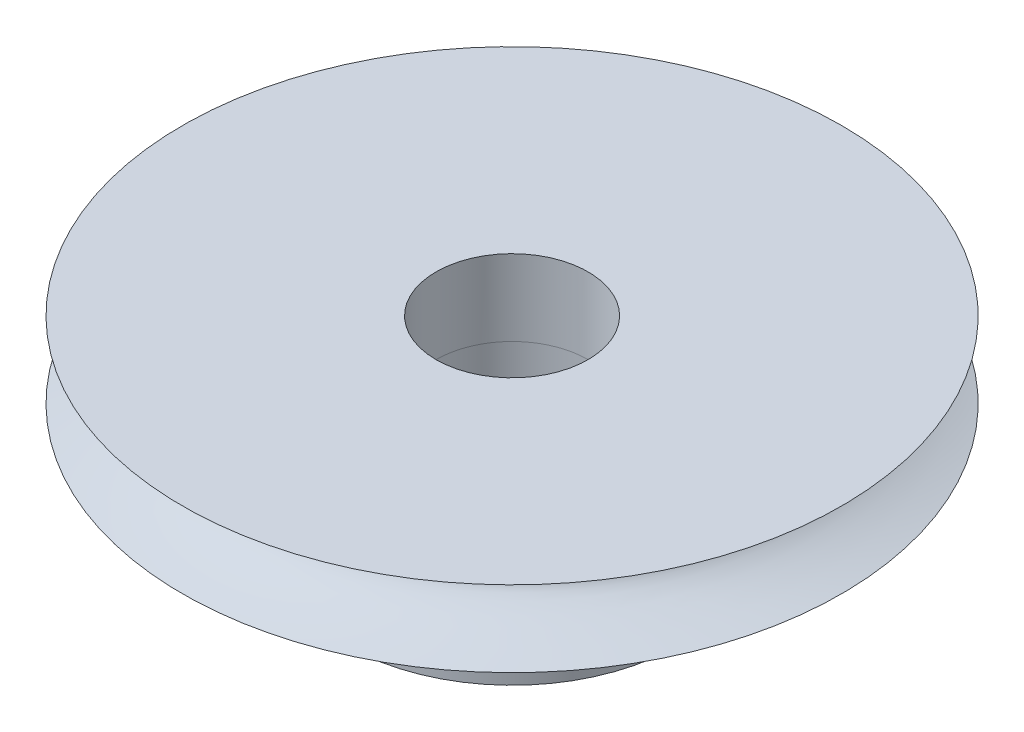
SolidWorks part; units mm, degrees
ref_plane "Front Plane" through (0, 0, 0) normal (0, 0, 1) x (1, 0, 0)
ref_plane "Top Plane" through (0, 0, 0) normal (0, 1, 0) x (1, 0, 0)
ref_plane "Right Plane" through (0, 0, 0) normal (1, 0, 0) x (0, 0, -1)
sketch "Sketch9" plane through (0, 0, 0) normal (0, 0, 1) x (1, 0, 0)
  line L0 (-4.7031, 0.0646) -> (0.1321, -1.2942) construction
  line L1 (-4.7031, -2.9354) -> (8.2969, -2.9354)
  line L3 (-4.7031, 0.0646) -> (8.2969, 0.0646)
  line L4 (8.2969, -2.9354) -> (8.2969, 0.0646)
  line L5 (0.1321, -1.2942) -> (-4.7031, -2.9354) construction
  spline S0 degree 2 poles (-4.7031, 0.0646) (0.1321, -1.2942) (-4.7031, -2.9354) knots 0 0 0 1 1 1
  dimension "D3" = 13
  dimension "D1" = 3
  dimension "D2" = 13
revolve "Revolve1" add sketch "Sketch9" angle 360 about L4
sketch "Sketch117" plane through (0, 0.0646, 0) normal (0, 1, 0) x (1, 0, 0)
  circle A0 centre (8.2969, 0) radius 3
extrude "Cut-Extrude4" cut sketch "Sketch117" against normal blind 3
sketch "Sketch122" plane through (0, -2.9354, 0) normal (0, -1, 0) x (-1, 0, 0)
  circle A0 centre (-8.2969, 0) radius 6.5398
extrude "Boss-Extrude1" add sketch "Sketch122" along normal blind 5
sketch "Sketch123" plane through (0, -2.9354, 0) normal (0, 1, 0) x (1, 0, 0)
  circle A0 centre (8.333, 0) radius 3.036
extrude "Cut-Extrude5" cut sketch "Sketch123" against normal blind 5
hole_wizard "M2x0.4 Tapped Hole1" positions "3DSketch1" profile "Sketch124" tap size "M2x0.4" standard "ANSI Metric" end condition through all
sketch3d "3DSketch1"
  circle A0 centre (8.2969, -2.9354, 0) radius 6.5398 construction
  circle A1 centre (8.2969, -7.9354, 0) radius 6.5398 construction
  point P0 (1.8154, -5.4316, -0.8709)
  point P5 (8.2969, -9.4751, 0)
  point P8 (8.2969, -14.4751, 0)
  dimension "D1" = 7
  dimension "D2" = 7.0027
sketch "Sketch124" plane through (1.8154, -5.4316, -0.8709) normal (0, 1, 0) x (-0.1332, 0, 0.9911)
  line L0 (0, 0) -> (0, 21.1551)
  line L1 (0, 21.1551) -> (0.8, 21.1551)
  line L2 (0.8, 21.1551) -> (0.8, 0)
  line L5 (0.8, 0) -> (0, 0)
  line L11 (0, -6.35) -> (0, 107.95) construction
  dimension "Thru Tap Drill Dia." = 1.6
  dimension "Thru Tap Drill Depth" = 21.1551
cosmetic thread "Hole Thread1" parameters "D2"=2
